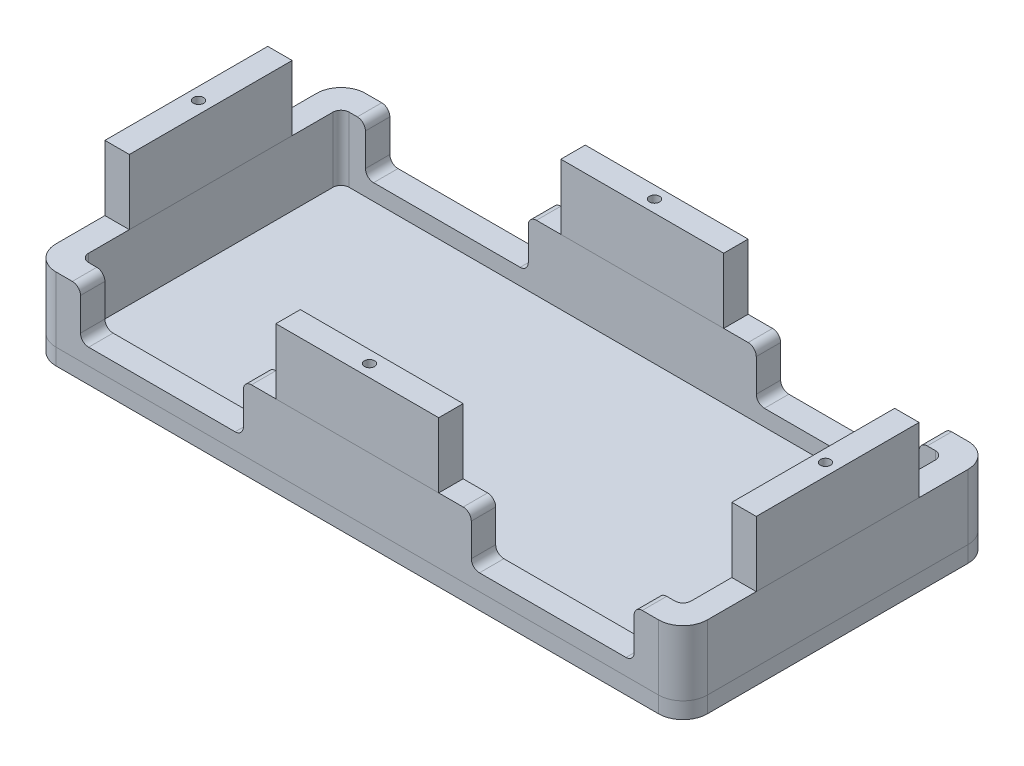
SolidWorks part; units mm, degrees
material "ABS"
ref_plane "Front Plane" through (0, 0, 0) normal (0, 0, 1) x (1, 0, 0)
ref_plane "Top Plane" through (0, 0, 0) normal (0, 1, 0) x (1, 0, 0)
ref_plane "Right Plane" through (0, 0, 0) normal (1, 0, 0) x (0, 0, -1)
sketch "Sketch1" plane through (0, 0, 0) normal (0, 1, 0) x (1, 0, 0)
  line L1 (-10, 19) -> (10, 19)
  line L2 (-10, 19) -> (-10, 16)
  line L3 (-10, 16) -> (10, 16)
  line L4 (10, 19) -> (10, 16)
  line L5 (-10, 19) -> (10, 16) construction
  line L6 (-10, 16) -> (10, 19) construction
  line L7 (-55, 0) -> (55, 0) construction
  line L8 (-40, -10) -> (-40, -19)
  line L14 (-40, -10) -> (-37, -10)
  line L15 (-40, -10) -> (-40, 10)
  line L16 (-40, 10) -> (-37, 10)
  line L17 (-37, -10) -> (-37, 10)
  line L18 (-40, -10) -> (-37, 10) construction
  line L19 (-40, 10) -> (-37, -10) construction
  line L20 (-37, -10) -> (-37, -16)
  line L21 (-10, -16) -> (10, -19) construction
  line L26 (-37, 10) -> (-37, 16)
  line L27 (-37, 16) -> (-10, 16)
  line L28 (-40, 10) -> (-40, 19)
  line L29 (-40, 19) -> (-10, 19)
  line L30 (-10, -19) -> (10, -16) construction
  line L31 (-40, -19) -> (-10, -19)
  line L32 (-37, -16) -> (-10, -16)
  line L33 (10, -19) -> (10, -16)
  line L34 (-10, -16) -> (10, -16)
  line L35 (-10, -19) -> (-10, -16)
  line L36 (-10, -19) -> (10, -19)
  line L37 (0, -55) -> (0, 55) construction
  line L38 (37, -16) -> (10, -16)
  line L39 (40, -19) -> (10, -19)
  line L40 (40, 10) -> (37, -10) construction
  line L41 (40, -10) -> (37, 10) construction
  line L42 (40, 19) -> (10, 19)
  line L43 (40, 10) -> (40, 19)
  line L44 (37, 16) -> (10, 16)
  line L45 (37, 10) -> (37, 16)
  line L46 (37, -10) -> (37, -16)
  line L47 (37, -10) -> (37, 10)
  line L48 (40, 10) -> (37, 10)
  line L49 (40, -10) -> (40, 10)
  line L50 (40, -10) -> (37, -10)
  line L51 (40, -10) -> (40, -19)
  point P0 (0, 17.5)
  point P14 (0, -17.5)
  point P15 (-38.5, 0)
  point P32 (38.5, 0)
  dimension "D1" = 3
  dimension "D2" = 20
  dimension "D3" = 17.5
  dimension "D4" = 38.5
  dimension "D5" = 20
extrude "Boss-Extrude1" add sketch "Sketch1" against normal blind 8 contours L29 L28 L16 L26 L27 L2 | L14 L17 L16 L15 | L31 L35 L32 L20 L14 L8 | L35 L36 L33 L34 | L51 L50 L46 L38 L33 L39 | L50 L49 L48 L47 | L48 L43 L42 L4 L44 L45 | L4 L1 L2 L3 region at (0, 0, -17.5) region at (-27.25, 0, -16.75) region at (27.25, 0, -16.75) region at (-38.5, 0, 0) region at (38.5, 0, 0) region at (-27.25, 0, 16.75) region at (27.25, 0, 16.75) region at (0, 0, 17.5)
extrude "Boss-Extrude4" add sketch "Sketch1<4>" along normal blind 8 separate body contours L14 L17 L16 L15 | L4 L1 L2 L3 | L35 L36 L33 L34 | L50 L49 L48 L47 region at (0, 0, -17.5) region at (-38.5, 0, 0) region at (38.5, 0, 0) region at (0, 0, 17.5)
sketch "Sketch1<4>" plane through (0, 0, 0) normal (0, 1, 0) x (1, 0, 0) same geometry as "Sketch1"
sketch "Sketch2" plane through (0, -8, 0) normal (0, -1, 0) x (1, 0, 0)
  line L1 (40, -19) -> (-40, -19)
  line L2 (40, -19) -> (40, 19)
  line L3 (40, 19) -> (-40, 19)
  line L4 (-40, -19) -> (-40, 19)
  line L5 (40, -19) -> (-40, 19) construction
  line L6 (40, 19) -> (-40, -19) construction
  line L8 (-40, 19) -> (40, 19) construction
  line L9 (-40, 19) -> (-40, -19) construction
  point P0 (0, 0)
extrude "Boss-Extrude2" add sketch "Sketch2" along normal blind 2 separate body
fillet "Fillet2" radius 3 4 edges at (40, -9, -19) (40, -9, 19) (-40, -9, -19) (-40, -9, 19)
fillet "Fillet1" radius 3 4 edges at (-40, -4, -19) (40, -4, -19) (40, -4, 19) (-40, -4, 19)
fillet "Fillet3" radius 1 4 edges at (37, -4, -16) (37, -4, 16) (-37, -4, -16) (-37, -4, 16)
sketch "Sketch3" [suppressed] plane through (0, -10, 0) normal (0, 1, 0) x (1, 0, 0)
  line L2 (37, -19) -> (-37, -19) construction
  line L3 (40, 16) -> (40, -16) construction
  line L4 (38, -10) -> (40, 16)
  line L5 (-37, -19) -> (10, -17)
  line L6 (37, -19) -> (-37, -19)
  line L7 (40, 16) -> (40, -16)
  line L8 (38, -12) -> (38, -12)
  line L9 (38, -12) -> (38, -16)
  line L10 (37, -17) -> (12, -17)
  line L11 (12, -17) -> (12, -17)
  line L12 (38, -10) -> (38, -12)
  line L13 (12, -17) -> (10, -17)
  line L15 (0, -11) -> (0, 11) construction
  line L16 (-12, -17) -> (-10, -17)
  line L17 (-38, -10) -> (-38, -12)
  line L18 (-37, -17) -> (-12, -17)
  line L19 (-38, -12) -> (-38, -16)
  line L20 (-40, 16) -> (-40, -16)
  line L21 (-37, -19) -> (37, -19)
  line L22 (37, -19) -> (-10, -17)
  line L23 (-38, -10) -> (-40, 16)
  line L24 (-11, 0) -> (11, 0) construction
  line L25 (-38, 10) -> (-40, -16)
  line L26 (37, 19) -> (-10, 17)
  line L27 (-37, 19) -> (37, 19)
  line L28 (-40, -16) -> (-40, 16)
  line L29 (-38, 12) -> (-38, 16)
  line L30 (-37, 17) -> (-12, 17)
  line L31 (-38, 10) -> (-38, 12)
  line L32 (-12, 17) -> (-10, 17)
  line L33 (12, 17) -> (10, 17)
  line L34 (38, 10) -> (38, 12)
  line L35 (37, 17) -> (12, 17)
  line L36 (38, 12) -> (38, 16)
  line L37 (40, -16) -> (40, 16)
  line L38 (37, 19) -> (-37, 19)
  line L39 (-37, 19) -> (10, 17)
  line L40 (38, 10) -> (40, -16)
  arc A1 (37, -19) -> (40, -16) centre (37, -16) ccw
  arc A2 (37, -17) -> (38, -16) centre (37, -16) ccw
  arc A3 (-37, -17) -> (-38, -16) centre (-37, -16) cw
  arc A4 (-37, -19) -> (-40, -16) centre (-37, -16) cw
  arc A5 (-37, 19) -> (-40, 16) centre (-37, 16) ccw
  arc A6 (-37, 17) -> (-38, 16) centre (-37, 16) ccw
  arc A7 (37, 17) -> (38, 16) centre (37, 16) cw
  arc A8 (37, 19) -> (40, 16) centre (37, 16) cw
  dimension "D1" = 2
sketch "Sketch4" plane through (0, 0, 19) normal (0, 0, 1) x (1, 0, 0)
  line L1 (-34, 0) -> (-14, 0)
  line L2 (-34, 0) -> (-34, -6)
  line L3 (-34, -6) -> (-14, -6)
  line L4 (-14, 0) -> (-14, -6)
  line L5 (-34, 0) -> (-14, -6) construction
  line L6 (-34, -6) -> (-14, 0) construction
  line L7 (-40, -8) -> (-40, 0) construction
  line L8 (-37, 0) -> (37, 0) construction
  line L9 (0, -9.9) -> (0, 9.9) construction
  line L10 (34, -6) -> (14, 0) construction
  line L11 (34, 0) -> (14, -6) construction
  line L12 (14, 0) -> (14, -6)
  line L13 (34, -6) -> (14, -6)
  line L14 (34, 0) -> (34, -6)
  line L15 (34, 0) -> (14, 0)
  point P0 (-24, -3)
  point P15 (24, -3)
  dimension "D1" = 20
  dimension "D2" = 6
  dimension "D3" = 6
extrude "Cut-Extrude1" cut sketch "Sketch4" against normal through all both and the other way through all
fillet "Fillet4" radius 1 16 edges at (14, -6, -17.5) (-34, -6, -17.5) (-14, -6, -17.5) (34, -6, -17.5) (34, 0, -17.5) (14, 0, -17.5) (34, 0, 17.5) (34, -6, 17.5) (14, -6, 17.5) (14, 0, 17.5) (-14, 0, 17.5) (-14, -6, 17.5) (-34, -6, 17.5) (-34, 0, 17.5) (-14, 0, -17.5) (-34, 0, -17.5)
hole_wizard "M1.6x0.35 Tapped Hole1" positions "Sketch5" profile "Sketch6" tap size "M1.6x0.35" standard "ANSI Metric"
sketch "Sketch5" plane through (0, 8, 0) normal (0, 1, 0) x (1, 0, 0)
  line L0 (38.5, 0) -> (0, 0) construction
  line L1 (0, 0) -> (-38.5, 0) construction
  line L3 (0, -17.5) -> (0, 0) construction
  line L4 (0, 0) -> (0, 17.5) construction
  point P0 (38.5, 0)
  point P2 (0, 17.5)
  point P4 (0, -17.5)
  point P6 (-38.5, 0)
  dimension "D1" = 38.5
  dimension "D2" = 17.5
sketch "Sketch6" plane through (38.5, 8, 0) normal (1, 0, 0) x (0, 0, 1)
  line L0 (0, 0) -> (0, 3.6255)
  line L1 (0, 3.6255) -> (0.625, 3.25)
  line L2 (0.625, 3.25) -> (0.625, 0)
  line L5 (0.625, 0) -> (0, 0)
  line L10 (0, 3.6255) -> (-0.625, 3.25) construction
  line L11 (0, -6.35) -> (0, 107.95) construction
  dimension "Tap Drill Dia." = 1.25
  dimension "Tap Drill Depth" = 3.25
  dimension "Drill Angle" = 118
cosmetic thread "Hole Thread1" parameters "D1"=3.2, "D2"=1.6
cosmetic thread "Hole Thread2" parameters "D1"=3.2, "D2"=1.6
cosmetic thread "Hole Thread3" parameters "D1"=3.2, "D2"=1.6
cosmetic thread "Hole Thread4" parameters "D1"=3.2, "D2"=1.6
